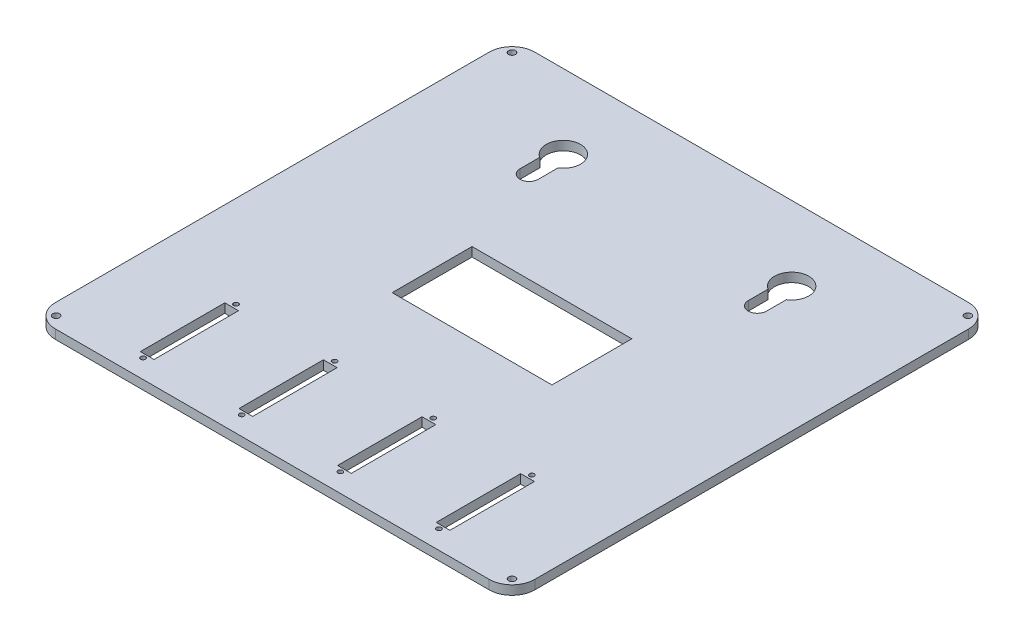
SolidWorks part; units mm, degrees
ref_plane "Front Plane" through (0, 0, 0) normal (0, 0, 1) x (1, 0, 0)
ref_plane "Top Plane" through (0, 0, 0) normal (0, 1, 0) x (1, 0, 0)
ref_plane "Right Plane" through (0, 0, 0) normal (1, 0, 0) x (0, 0, -1)
sketch "Sketch1" plane through (0, 0, 0) normal (0, 1, 0) x (1, 0, 0)
  line L0 (-101, -101) -> (-101, 101)
  line L5 (-105, -105) -> (105, -105)
  line L6 (-105, -105) -> (-105, 105)
  line L7 (-105, 105) -> (105, 105)
  line L8 (105, -105) -> (105, 105)
  line L9 (-101, 101) -> (101, 101)
  line L10 (101, -101) -> (101, 101)
  line L11 (-101, -101) -> (101, -101)
  line L12 (-101, 101) -> (-99.8333, 99.8333) construction
  line L13 (-55, 0) -> (55, 0) construction
  line L14 (-101, -101) -> (-99.8333, -99.8333) construction
  line L15 (0, -55) -> (0, 55) construction
  line L16 (101, -101) -> (99.8333, -99.8333) construction
  line L17 (101, 101) -> (99.8333, 99.8333) construction
  circle A1 centre (-99.8333, 99.8333) radius 1.5
  circle A2 centre (-99.8333, -99.8333) radius 1.5
  circle A3 centre (99.8333, -99.8333) radius 1.5
  circle A4 centre (99.8333, 99.8333) radius 1.5
  point P0 (0, 0)
  point P6 (-105, 0)
  point P7 (0, 105)
  dimension "D3" = 4
  dimension "D4" = 3
  dimension "D1" = 210
  dimension "D2" = 210
  dimension "D5" = 1.65
  dimension "D6" = 45
extrude "MainExtrude" add sketch "Sketch1" along normal mid plane 4 contours L6 L5 L8 L7
extrude "ScrewHoles" cut sketch "Sketch1<6>" along normal mid plane 4 contours A1 | A2 | A3 | A4
sketch "Sketch1<6>" plane through (0, 0, 0) normal (0, 1, 0) x (1, 0, 0) same geometry as "Sketch1"
fillet "RoundedCorners" radius 10 4 edges at (-105, 0, -105) (-105, 0, 105) (105, 0, -105) (105, 0, 105)
sketch "Sketch2" plane through (0, 2, 0) normal (0, 1, 0) x (1, 0, 0)
  line L0 (-50, 72.5) -> (-50, 57.5) construction
  line L1 (-67.8, -58) -> (-61.8, -58)
  line L2 (-67.8, -58) -> (-67.8, -95)
  line L3 (-67.8, -95) -> (-61.8, -95)
  line L4 (-61.8, -58) -> (-61.8, -95)
  line L5 (-24.6, -58) -> (-18.6, -58)
  line L6 (-24.6, -58) -> (-24.6, -95)
  line L7 (-24.6, -95) -> (-18.6, -95)
  line L8 (-18.6, -58) -> (-18.6, -95)
  line L9 (18.6, -58) -> (24.6, -58)
  line L10 (18.6, -58) -> (18.6, -95)
  line L11 (18.6, -95) -> (24.6, -95)
  line L12 (24.6, -58) -> (24.6, -95)
  line L13 (61.8, -58) -> (67.8, -58)
  line L14 (61.8, -58) -> (61.8, -95)
  line L15 (61.8, -95) -> (67.8, -95)
  line L16 (67.8, -58) -> (67.8, -95)
  line L17 (-95, -105) -> (95, -105) construction
  line L19 (-67.8, -58) -> (-105, -58) construction
  line L20 (-105, -95) -> (-105, 95) construction
  line L21 (-61.8, -58) -> (-24.6, -58) construction
  line L22 (-18.6, -58) -> (18.6, -58) construction
  line L23 (24.6, -58) -> (61.8, -58) construction
  line L25 (-105, 65) -> (-50, 65) construction
  line L26 (-95, 105) -> (95, 105) construction
  line L30 (-54, 57.5) -> (-54, 66.1557)
  line L31 (-46, 57.5) -> (-46, 66.1557)
  line L32 (0, -2.2) -> (0, 2.2) construction
  line L33 (46, 57.5) -> (46, 66.1557)
  line L34 (54, 57.5) -> (54, 66.1557)
  line L36 (35, -17.5) -> (-35, -17.5)
  line L37 (35, -17.5) -> (35, 17.5)
  line L38 (35, 17.5) -> (-35, 17.5)
  line L39 (-35, -17.5) -> (-35, 17.5)
  arc A0 (-54, 57.5) -> (-46, 57.5) centre (-50, 57.5) ccw
  arc A4 (-46, 66.1557) -> (-54, 66.1557) centre (-50, 72.5) ccw
  arc A5 (54, 57.5) -> (46, 57.5) centre (50, 57.5) cw
  arc A6 (46, 66.1557) -> (54, 66.1557) centre (50, 72.5) cw
  circle A7 centre (-64.8, -96.8) radius 1.05
  circle A8 centre (-64.8, -56.1) radius 1.05
  circle A9 centre (-21.6, -56.1) radius 1.05
  circle A10 centre (-21.6, -96.8) radius 1.05
  circle A11 centre (21.6, -56.1) radius 1.05
  circle A12 centre (21.6, -96.8) radius 1.05
  circle A13 centre (64.8, -56.1) radius 1.05
  circle A14 centre (64.8, -96.8) radius 1.05
  point P30 (0, 17.5)
  point P40 (-50, 65)
  point P42 (0, 0)
  point P48 (-35, 0)
  point P54 (-64.8, -95)
  point P58 (-61.8, -76.5)
  point P59 (-64.8, -58)
  point P60 (-21.6, -58)
  point P71 (-21.6, -95)
  dimension "D7" = 15
  dimension "D8" = 4
  dimension "D16" = 2.1
  dimension "D17" = 43.2
  dimension "D18" = 4
  dimension "D1" = 6
  dimension "D2" = 37
  dimension "D3" = 37.2
  dimension "D4" = 10
  dimension "D5" = 55
  dimension "D6" = 40
  dimension "D9" = 15
  dimension "D10" = 70
  dimension "D11" = 35
  dimension "D12" = 50
  dimension "D13" = 57.5
  dimension "D14" = 40.7
  dimension "D15" = 20.3
  dimension "D19" = 1.9
  dimension "D20" = 1.8
extrude "Knotches/Sliders" cut sketch "Sketch2" against normal up to surface (4 mm away) up to face at (-99.8333, -2, 98.3333)
sketch "Sketch6" plane through (71.6843, -2, 14.4809) normal (0, -1, 0) x (1, 0, 0)
  line L0 (-22.5243, 23.5191) -> (13.3157, 23.5191) construction
  line L1 (33.3157, 80.5191) -> (33.3157, -109.4809) construction
  line L2 (-9.8843, 43.5191) -> (-3.8843, 43.5191) construction
  circle A0 centre (-22.5243, 23.5191) radius 0.98
  circle A1 centre (-22.5243, 23.5191) radius 2
  circle A2 centre (13.3157, 23.5191) radius 2
  circle A3 centre (13.3157, 23.5191) radius 0.98
  circle A4 centre (-22.5243, -50.7509) radius 2
  circle A5 centre (-22.5243, -50.7509) radius 0.98
  circle A6 centre (13.3157, -50.7509) radius 0.98
  circle A7 centre (13.3157, -50.7509) radius 2
  dimension "D1" = 1.96
  dimension "D2" = 4
  dimension "D4" = 74.27
  dimension "D5" = 35.84
  dimension "D6" = 20
  dimension "D7" = 20
  dimension "D3" = 2
extrude "PCBHoles" add sketch "Sketch6" along normal blind 4
fillet "PCBRounds" radius 2 4 edges at (85, -2, -34.27) (49.16, -2, -34.27) (85, -2, 40) (49.16, -2, 40)
